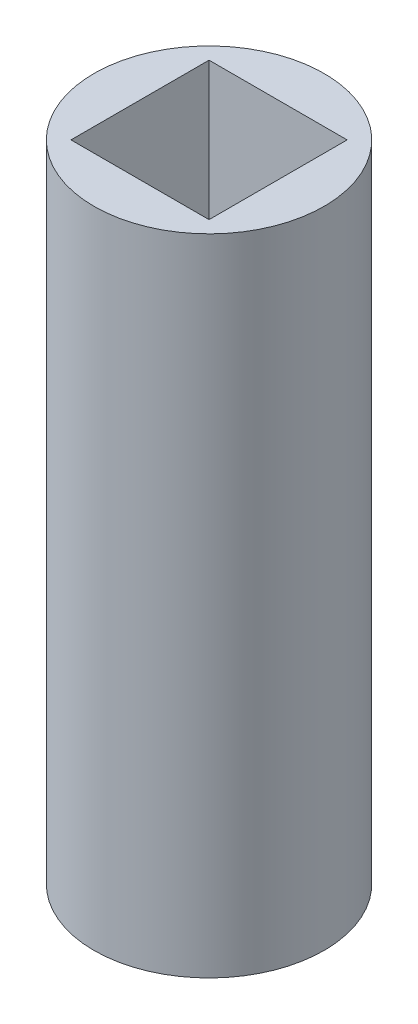
SolidWorks part; units mm, degrees
material "PLA"
ref_plane "Front" through (0, 0, 0) normal (0, 0, 1) x (1, 0, 0)
ref_plane "Top" through (0, 0, 0) normal (0, 1, 0) x (1, 0, 0)
ref_plane "Right" through (0, 0, 0) normal (1, 0, 0) x (0, 0, -1)
sketch "Sketch1" plane through (0, 0, 0) normal (0, 1, 0) x (1, 0, 0)
  circle A0 centre (0, 0) radius 15.875
  dimension "D1" = 31.75
extrude "Boss-Extrude1" add sketch "Sketch1" along normal blind 88.9
sketch "Sketch2" plane through (0, 88.9, 0) normal (0, 1, 0) x (1, 0, 0)
  line L1 (9.525, -9.525) -> (-9.525, -9.525)
  line L2 (9.525, -9.525) -> (9.525, 9.525)
  line L3 (9.525, 9.525) -> (-9.525, 9.525)
  line L4 (-9.525, -9.525) -> (-9.525, 9.525)
  line L5 (9.525, -9.525) -> (-9.525, 9.525) construction
  line L6 (9.525, 9.525) -> (-9.525, -9.525) construction
  point P0 (0, 0)
  dimension "D1" = 19.05
  dimension "D2" = 19.05
extrude "Cut-Extrude1" cut sketch "Sketch2" against normal blind 172.72
